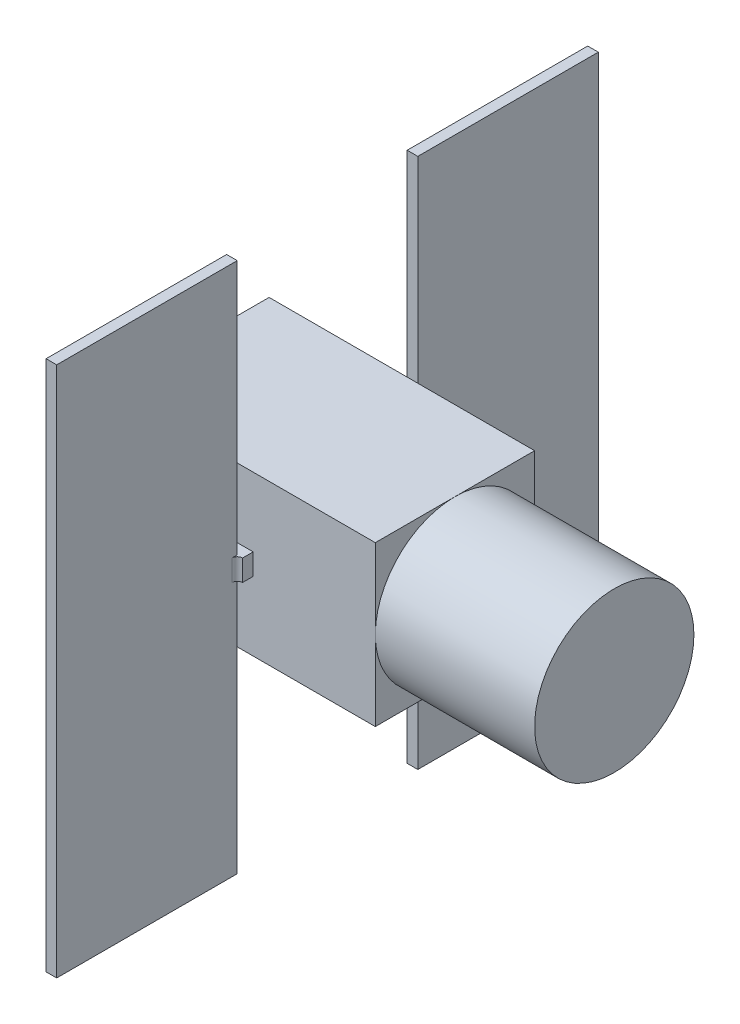
SolidWorks part; units mm, degrees
ref_plane "Front Plane" through (0, 0, 0) normal (0, 0, 1) x (1, 0, 0)
ref_plane "Top Plane" through (0, 0, 0) normal (0, 1, 0) x (1, 0, 0)
ref_plane "Right Plane" through (0, 0, 0) normal (1, 0, 0) x (0, 0, -1)
sketch "Sketch1" plane through (0, 0, 0) normal (0, 0, 1) x (1, 0, 0)
  line L1 (-250, -150) -> (250, -150)
  line L2 (-250, -150) -> (-250, 150)
  line L3 (-250, 150) -> (250, 150)
  line L4 (250, -150) -> (250, 150)
  line L5 (-250, -150) -> (250, 150) construction
  line L6 (-250, 150) -> (250, -150) construction
  point P0 (0, 0)
  dimension "D1" = 500
  dimension "D2" = 300
extrude "Boss-Extrude1" add sketch "Sketch1" along normal blind 150 and the other way blind 150
sketch "Sketch2" plane through (0, 0, 150) normal (0, 0, 1) x (1, 0, 0)
  line L1 (-20, -20) -> (20, -20)
  line L2 (-20, -20) -> (-20, 20)
  line L3 (-20, 20) -> (20, 20)
  line L4 (20, -20) -> (20, 20)
  line L5 (-20, -20) -> (20, 20) construction
  line L6 (-20, 20) -> (20, -20) construction
  point P0 (0, 0)
  dimension "D1" = 40
  dimension "D2" = 40
extrude "Boss-Extrude2" add sketch "Sketch2" along normal blind 20
sketch "Sketch3" plane through (0, 0, 170) normal (0, 0, 1) x (1, 0, 0)
  line L1 (-10, -500) -> (10, -500)
  line L2 (-10, -500) -> (-10, 500)
  line L3 (-10, 500) -> (10, 500)
  line L4 (10, -500) -> (10, 500)
  line L5 (-10, -500) -> (10, 500) construction
  line L6 (-10, 500) -> (10, -500) construction
  point P0 (0, 0)
  dimension "D1" = 1000
  dimension "D2" = 20
extrude "Boss-Extrude3" add sketch "Sketch3" along normal blind 340
fillet "Fillet1" radius 10 2 edges at (-10, 0, 170) (10, 0, 170)
sketch "Sketch4" plane through (-250, 0, 0) normal (-1, 0, 0) x (0, 0, 1)
  line L0 (0, 0) -> (58.044, 0) construction
  circle A0 centre (58.044, 0) radius 40
  dimension "D1" = 80
extrude "Boss-Extrude4" add sketch "Sketch4" along normal blind 150
sketch "Sketch5" plane through (-400, 0, 0) normal (-1, 0, 0) x (0, 0, 1)
  circle A0 centre (58.044, 0) radius 10
  dimension "D1" = 20
extrude "Boss-Extrude5" add sketch "Sketch5" along normal blind 50
mirror "Mirror1" about plane through (0, 0, 0) normal (0, 0, 1) of "Boss-Extrude5", "Boss-Extrude4", "Fillet1", "Boss-Extrude3", "Boss-Extrude2"
sketch "Sketch7" plane through (250, 0, 0) normal (1, 0, 0) x (0, 0, -1)
  circle A0 centre (0, 0) radius 150
  dimension "D1" = 300
extrude "Boss-Extrude6" add sketch "Sketch7" along normal blind 300
